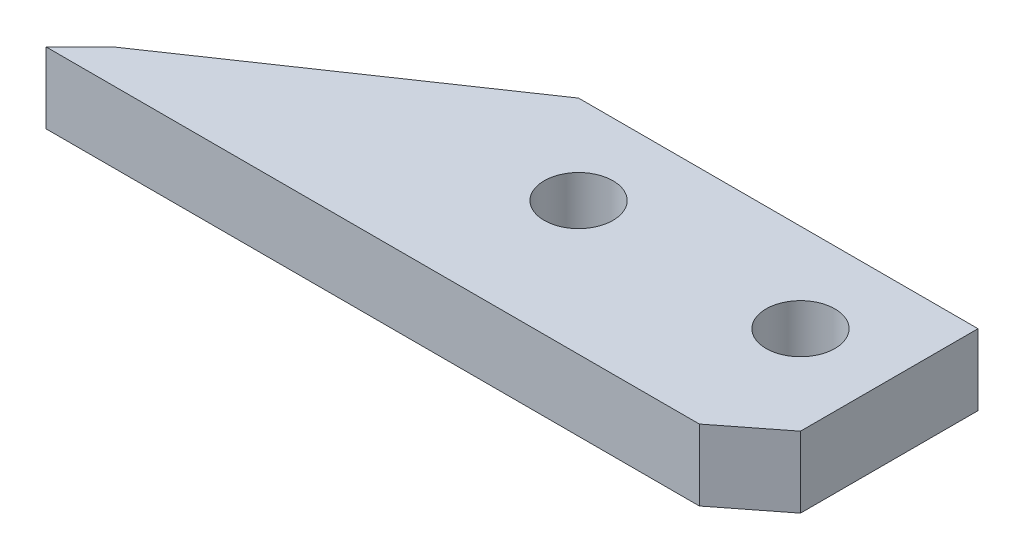
SolidWorks part; units mm, degrees
ref_plane "Front Plane" through (0, 0, 0) normal (0, 0, 1) x (1, 0, 0)
ref_plane "Top Plane" through (0, 0, 0) normal (0, 1, 0) x (1, 0, 0)
ref_plane "Right Plane" through (0, 0, 0) normal (1, 0, 0) x (0, 0, -1)
sketch "Sketch1" plane through (0, 0, 0) normal (0, 1, 0) x (1, 0, 0)
  line L0 (0, 0) -> (-25, -17)
  line L1 (-25, -17) -> (-28, -20)
  line L2 (-28, -20) -> (-10.3602, -20)
  line L5 (36, -16) -> (36, 0)
  line L6 (36, 0) -> (0, 0)
  line L8 (36, -16) -> (30.8813, -20)
  line L9 (30.8813, -20) -> (-10.3602, -20)
  circle A0 centre (28, -8) radius 3.1
  circle A1 centre (8, -8) radius 3.1
  dimension "D8" = 6.2
  dimension "D9" = 6.2
  dimension "D1" = 16
  dimension "D2" = 36
  dimension "D3" = 8
  dimension "D4" = 25
  dimension "D5" = 3
  dimension "D6" = 3
  dimension "D7" = 17
  dimension "D10" = 20
extrude "Boss-Extrude1" add sketch "Sketch1" along normal blind 6.4
